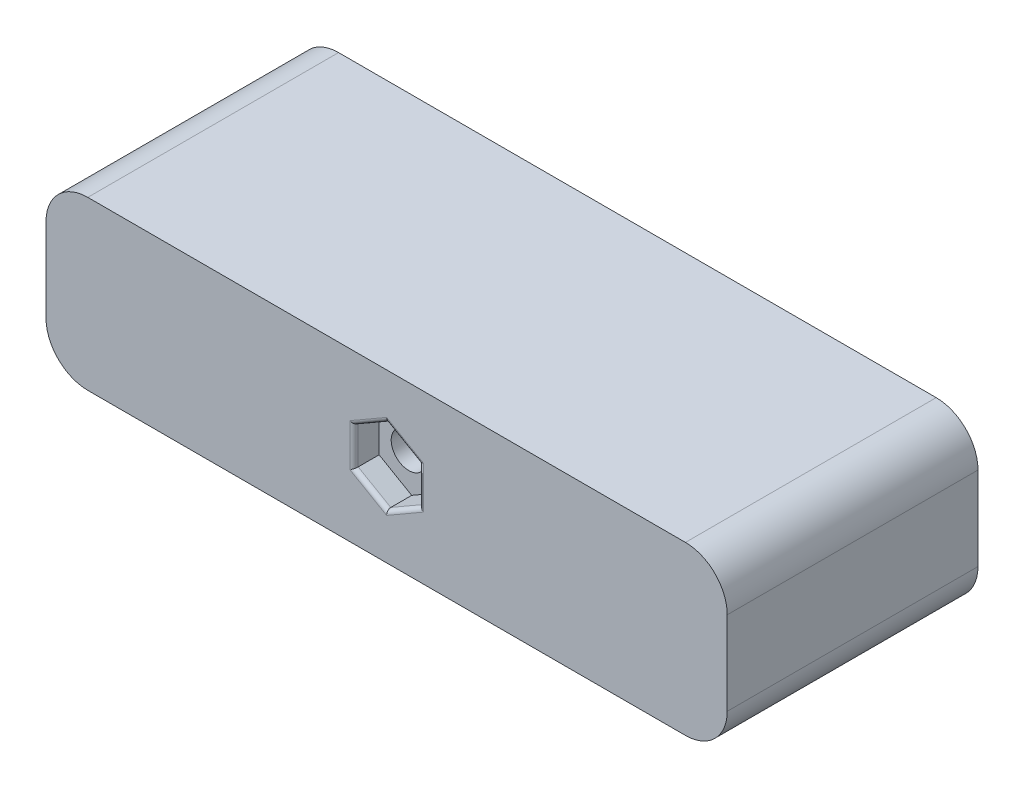
SolidWorks part; units mm, degrees
material "PVC 0.007 plastifié"
ref_plane "Plan de face" through (0, 0, 0) normal (0, 0, 1) x (1, 0, 0)
ref_plane "Plan de dessus" through (0, 0, 0) normal (0, 1, 0) x (1, 0, 0)
ref_plane "Plan de droite" through (0, 0, 0) normal (1, 0, 0) x (0, 0, -1)
sketch "Esquisse1" plane through (0, 0, 0) normal (0, 0, 1) x (1, 0, 0)
  line L1 (0, 0) -> (-81.5, 0)
  line L2 (0, 0) -> (0, 20)
  line L3 (0, 20) -> (-81.5, 20)
  line L4 (-81.5, 0) -> (-81.5, 20)
  dimension "D1" = 81.5
  dimension "D2" = 20
extrude "Boss.-Extru.1" add sketch "Esquisse1" along normal blind 30
sketch "Esquisse4" plane through (0, 0, 30) normal (0, 0, 1) x (1, 0, 0)
  line L0 (0, 20) -> (-81.5, 20) construction
  line L1 (-81.5, 20) -> (-81.5, 0) construction
  point P0 (-40.75, 20)
  point P1 (-81.5, 10)
sketch "Esquisse2" plane through (0, 0, 30) normal (0, 0, 1) x (1, 0, 0)
  line L0 (0, 0) -> (0, 20) construction
  line L1 (-40.75, 5.4967) -> (-36.85, 7.7483)
  line L2 (-36.85, 7.7483) -> (-36.85, 12.2517)
  line L3 (-36.85, 12.2517) -> (-40.75, 14.5033)
  line L4 (-40.75, 14.5033) -> (-44.65, 12.2517)
  line L5 (-44.65, 12.2517) -> (-44.65, 7.7483)
  line L6 (-44.65, 7.7483) -> (-40.75, 5.4967)
  circle A0 centre (-40.75, 10) radius 3.9 construction
  dimension "D1" = 7.8
extrude "Enlèv. mat.-Extru.1" cut sketch "Esquisse2" against normal blind 3
fillet "Congé1" radius 5 4 edges at (-81.5, 0, 15) (-81.5, 20, 15) (0, 0, 15) (0, 20, 15)
sketch "Esquisse3" plane through (0, 0, 30) normal (0, 0, 1) x (1, 0, 0)
  line L0 (0, 5) -> (0, 15) construction
  line L1 (-81.5, 15) -> (-81.5, 5) construction
  circle A0 centre (-10, 9.9745) radius 10
  circle A1 centre (-71.5, 9.9745) radius 9.9745
  dimension "D1" = 20
  dimension "D2" = 10
  dimension "D3" = 10
fillet "Congé2" radius 0.5 6 edges at (-44.65, 10, 30) (-42.7, 6.6225, 30) (-38.8, 6.6225, 30) (-36.85, 10, 30) (-38.8, 13.3775, 30) (-42.7, 13.3775, 30)
sketch "Esquisse8" plane through (0, 0, 0) normal (0, 0, 1) x (1, 0, 0)
  line L0 (0, 5) -> (0, 15) construction
  circle A0 centre (-41.1, 10) radius 2.1038
  dimension "D1" = 10
  dimension "D2" = 41.1
extrude "Enlèv. mat.-Extru.3" cut sketch "Esquisse8" along normal through all
